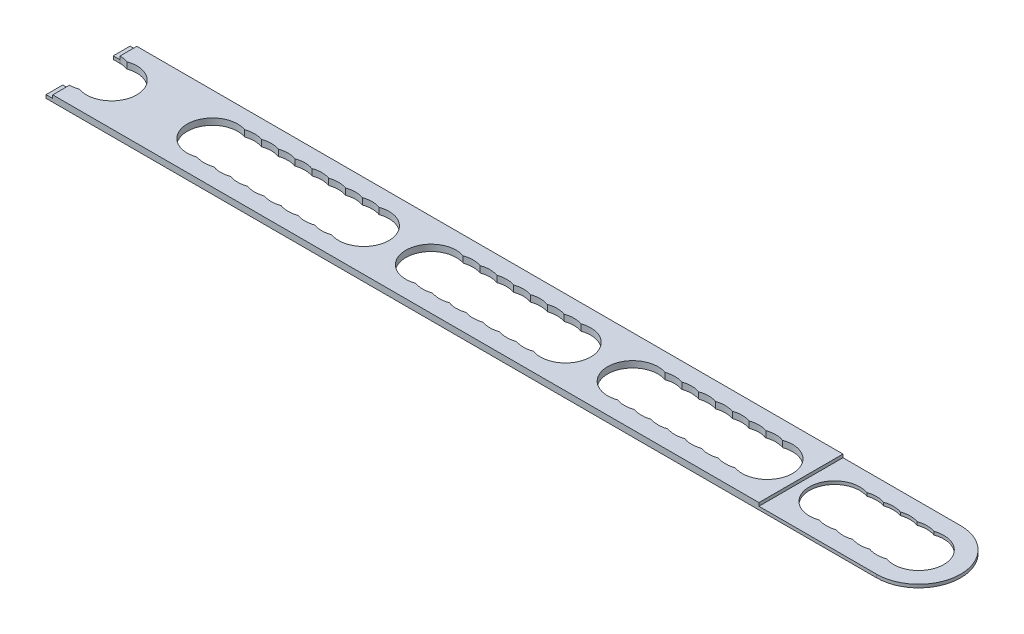
SolidWorks part; units mm, degrees
note: The reader was unsure of these and kept them because the rebuilt part matched: shared geometry of "Sketch1<3>".
ref_plane "Front Plane" through (0, 0, 0) normal (0, 0, 1) x (1, 0, 0)
ref_plane "Top Plane" through (0, 0, 0) normal (0, 1, 0) x (1, 0, 0)
ref_plane "Right Plane" through (0, 0, 0) normal (1, 0, 0) x (0, 0, -1)
sketch "Sketch1" plane through (0, 0, 0) normal (0, 1, 0) x (1, 0, 0)
  line L0 (-247.5, 0) -> (247.5, 0) construction
  line L1 (-247.5, -12.5) -> (247.5, -12.5)
  line L2 (-247.5, -12.5) -> (-247.5, 12.5)
  line L3 (-247.5, 12.5) -> (247.5, 12.5)
  line L4 (247.5, -12.5) -> (247.5, 12.5) construction
  line L5 (-247.5, -12.5) -> (247.5, 12.5) construction
  line L6 (-247.5, 12.5) -> (247.5, -12.5) construction
  line L7 (0, 12.5) -> (0, -12.5)
  line L8 (30, 12.5) -> (30, -12.5) construction
  line L9 (90, 12.5) -> (90, -12.5) construction
  line L10 (150, 12.5) -> (150, -12.5) construction
  line L11 (210, 12.5) -> (210, -12.5)
  arc A0 (-2.5, 7.0711) -> (2.5, 7.0711) centre (0, 0) cw
  arc A1 (2.5, 7.0711) -> (7.5, 7.0711) centre (5, 0) cw
  arc A2 (7.5, 7.0711) -> (12.5, 7.0711) centre (10, 0) cw
  arc A3 (12.5, 7.0711) -> (17.5, 7.0711) centre (15, 0) cw
  arc A4 (17.5, 7.0711) -> (22.5, 7.0711) centre (20, 0) cw
  arc A5 (22.5, 7.0711) -> (27.5, 7.0711) centre (25, 0) cw
  arc A6 (27.5, 7.0711) -> (32.5, 7.0711) centre (30, 0) cw
  arc A7 (32.5, 7.0711) -> (37.5, 7.0711) centre (35, 0) cw
  arc A8 (37.5, 7.0711) -> (42.5, 7.0711) centre (40, 0) cw
  arc A9 (42.5, 7.0711) -> (47.5, 7.0711) centre (45, 0) cw
  arc A10 (47.5, 7.0711) -> (52.5, 7.0711) centre (50, 0) cw
  arc A11 (52.5, 7.0711) -> (57.5, 7.0711) centre (55, 0) cw
  arc A12 (57.5, 7.0711) -> (62.5, 7.0711) centre (60, 0) cw
  arc A13 (62.5, 7.0711) -> (67.5, 7.0711) centre (65, 0) cw
  arc A14 (67.5, 7.0711) -> (72.5, 7.0711) centre (70, 0) cw
  arc A15 (72.5, 7.0711) -> (77.5, 7.0711) centre (75, 0) cw
  arc A16 (77.5, 7.0711) -> (82.5, 7.0711) centre (80, 0) cw
  arc A17 (82.5, 7.0711) -> (87.5, 7.0711) centre (85, 0) cw
  arc A18 (87.5, 7.0711) -> (92.5, 7.0711) centre (90, 0) cw
  arc A19 (92.5, 7.0711) -> (97.5, 7.0711) centre (95, 0) cw
  arc A20 (97.5, 7.0711) -> (102.5, 7.0711) centre (100, 0) cw
  arc A21 (102.5, 7.0711) -> (107.5, 7.0711) centre (105, 0) cw
  arc A22 (107.5, 7.0711) -> (112.5, 7.0711) centre (110, 0) cw
  arc A23 (112.5, 7.0711) -> (117.5, 7.0711) centre (115, 0) cw
  arc A24 (117.5, 7.0711) -> (122.5, 7.0711) centre (120, 0) cw
  arc A25 (122.5, 7.0711) -> (127.5, 7.0711) centre (125, 0) cw
  arc A26 (127.5, 7.0711) -> (132.5, 7.0711) centre (130, 0) cw
  arc A27 (132.5, 7.0711) -> (137.5, 7.0711) centre (135, 0) cw
  arc A28 (137.5, 7.0711) -> (142.5, 7.0711) centre (140, 0) cw
  arc A29 (142.5, 7.0711) -> (147.5, 7.0711) centre (145, 0) cw
  arc A30 (147.5, 7.0711) -> (152.5, 7.0711) centre (150, 0) cw
  arc A31 (152.5, 7.0711) -> (157.5, 7.0711) centre (155, 0) cw
  arc A32 (157.5, 7.0711) -> (162.5, 7.0711) centre (160, 0) cw
  arc A33 (162.5, 7.0711) -> (167.5, 7.0711) centre (165, 0) cw
  arc A34 (167.5, 7.0711) -> (172.5, 7.0711) centre (170, 0) cw
  arc A35 (172.5, 7.0711) -> (177.5, 7.0711) centre (175, 0) cw
  arc A36 (177.5, 7.0711) -> (182.5, 7.0711) centre (180, 0) cw
  arc A37 (182.5, 7.0711) -> (187.5, 7.0711) centre (185, 0) cw
  arc A38 (187.5, 7.0711) -> (192.5, 7.0711) centre (190, 0) cw
  arc A39 (192.5, 7.0711) -> (197.5, 7.0711) centre (195, 0) cw
  arc A40 (197.5, 7.0711) -> (202.5, 7.0711) centre (200, 0) cw
  arc A41 (202.5, 7.0711) -> (207.5, 7.0711) centre (205, 0) cw
  arc A42 (207.5, 7.0711) -> (212.5, 7.0711) centre (210, 0) cw
  arc A43 (212.5, 7.0711) -> (217.5, 7.0711) centre (215, 0) cw
  arc A44 (217.5, 7.0711) -> (222.5, 7.0711) centre (220, 0) cw
  arc A45 (222.5, 7.0711) -> (227.5, 7.0711) centre (225, 0) cw
  arc A46 (227.5, 7.0711) -> (232.5, 7.0711) centre (230, 0) cw
  arc A47 (232.5, 7.0711) -> (237.5, 7.0711) centre (235, 0) cw
  arc A48 (222.5, -7.0711) -> (227.5, -7.0711) centre (225, 0) ccw
  arc A49 (217.5, -7.0711) -> (222.5, -7.0711) centre (220, 0) ccw
  arc A50 (212.5, -7.0711) -> (217.5, -7.0711) centre (215, 0) ccw
  arc A51 (207.5, -7.0711) -> (212.5, -7.0711) centre (210, 0) ccw
  arc A52 (202.5, -7.0711) -> (207.5, -7.0711) centre (205, 0) ccw
  arc A53 (197.5, -7.0711) -> (202.5, -7.0711) centre (200, 0) ccw
  arc A54 (192.5, -7.0711) -> (197.5, -7.0711) centre (195, 0) ccw
  arc A55 (187.5, -7.0711) -> (192.5, -7.0711) centre (190, 0) ccw
  arc A56 (182.5, -7.0711) -> (187.5, -7.0711) centre (185, 0) ccw
  arc A57 (177.5, -7.0711) -> (182.5, -7.0711) centre (180, 0) ccw
  arc A58 (172.5, -7.0711) -> (177.5, -7.0711) centre (175, 0) ccw
  arc A59 (167.5, -7.0711) -> (172.5, -7.0711) centre (170, 0) ccw
  arc A60 (162.5, -7.0711) -> (167.5, -7.0711) centre (165, 0) ccw
  arc A61 (157.5, -7.0711) -> (162.5, -7.0711) centre (160, 0) ccw
  arc A62 (152.5, -7.0711) -> (157.5, -7.0711) centre (155, 0) ccw
  arc A63 (147.5, -7.0711) -> (152.5, -7.0711) centre (150, 0) ccw
  arc A64 (142.5, -7.0711) -> (147.5, -7.0711) centre (145, 0) ccw
  arc A65 (137.5, -7.0711) -> (142.5, -7.0711) centre (140, 0) ccw
  arc A66 (132.5, -7.0711) -> (137.5, -7.0711) centre (135, 0) ccw
  arc A67 (127.5, -7.0711) -> (132.5, -7.0711) centre (130, 0) ccw
  arc A68 (122.5, -7.0711) -> (127.5, -7.0711) centre (125, 0) ccw
  arc A69 (117.5, -7.0711) -> (122.5, -7.0711) centre (120, 0) ccw
  arc A70 (112.5, -7.0711) -> (117.5, -7.0711) centre (115, 0) ccw
  arc A71 (107.5, -7.0711) -> (112.5, -7.0711) centre (110, 0) ccw
  arc A72 (102.5, -7.0711) -> (107.5, -7.0711) centre (105, 0) ccw
  arc A73 (97.5, -7.0711) -> (102.5, -7.0711) centre (100, 0) ccw
  arc A74 (92.5, -7.0711) -> (97.5, -7.0711) centre (95, 0) ccw
  arc A75 (87.5, -7.0711) -> (92.5, -7.0711) centre (90, 0) ccw
  arc A76 (82.5, -7.0711) -> (87.5, -7.0711) centre (85, 0) ccw
  arc A77 (77.5, -7.0711) -> (82.5, -7.0711) centre (80, 0) ccw
  arc A78 (72.5, -7.0711) -> (77.5, -7.0711) centre (75, 0) ccw
  arc A79 (67.5, -7.0711) -> (72.5, -7.0711) centre (70, 0) ccw
  arc A80 (62.5, -7.0711) -> (67.5, -7.0711) centre (65, 0) ccw
  arc A81 (57.5, -7.0711) -> (62.5, -7.0711) centre (60, 0) ccw
  arc A82 (52.5, -7.0711) -> (57.5, -7.0711) centre (55, 0) ccw
  arc A83 (47.5, -7.0711) -> (52.5, -7.0711) centre (50, 0) ccw
  arc A84 (42.5, -7.0711) -> (47.5, -7.0711) centre (45, 0) ccw
  arc A85 (37.5, -7.0711) -> (42.5, -7.0711) centre (40, 0) ccw
  arc A86 (32.5, -7.0711) -> (37.5, -7.0711) centre (35, 0) ccw
  arc A87 (27.5, -7.0711) -> (32.5, -7.0711) centre (30, 0) ccw
  arc A88 (22.5, -7.0711) -> (27.5, -7.0711) centre (25, 0) ccw
  arc A89 (17.5, -7.0711) -> (22.5, -7.0711) centre (20, 0) ccw
  arc A90 (12.5, -7.0711) -> (17.5, -7.0711) centre (15, 0) ccw
  arc A91 (7.5, -7.0711) -> (12.5, -7.0711) centre (10, 0) ccw
  arc A92 (2.5, -7.0711) -> (7.5, -7.0711) centre (5, 0) ccw
  arc A93 (-2.5, -7.0711) -> (2.5, -7.0711) centre (0, 0) ccw
  arc A94 (237.5, 7.0711) -> (242.5, 7.0711) centre (240, 0) cw
  arc A96 (7.5, 7.0711) -> (7.5, -7.0711) centre (5, 0) cw
  arc A97 (32.5, 7.0711) -> (32.5, -7.0711) centre (35, 0) ccw
  arc A98 (82.5, 7.0711) -> (82.5, -7.0711) centre (80, 0) cw
  arc A99 (97.5, 7.0711) -> (97.5, -7.0711) centre (100, 0) ccw
  arc A100 (142.5, 7.0711) -> (142.5, -7.0711) centre (140, 0) cw
  arc A101 (157.5, 7.0711) -> (157.5, -7.0711) centre (160, 0) ccw
  arc A102 (242.5, 7.0711) -> (247.5, 7.0711) centre (245, 0) cw
  arc A103 (242.5, -7.0711) -> (247.5, -7.0711) centre (245, 0) ccw
  arc A104 (237.5, -7.0711) -> (242.5, -7.0711) centre (240, 0) ccw
  arc A105 (232.5, -7.0711) -> (237.5, -7.0711) centre (235, 0) ccw
  arc A106 (227.5, -7.0711) -> (232.5, -7.0711) centre (230, 0) ccw
  arc A107 (247.5, 7.0711) -> (247.5, -7.0711) centre (245, 0) cw
  arc A108 (245, 12.5) -> (245, -12.5) centre (245, 0) cw
  arc A109 (202.5, 7.0711) -> (202.4833, -7.077) centre (200, 0) cw
  arc A110 (217.5, 7.0711) -> (217.5, -7.0711) centre (220, 0) ccw
  point P0 (0, 0)
  dimension "D4" = 7.5
  dimension "D1" = 25
  dimension "D2" = 495
  dimension "D3" = 5
  dimension "D6" = 30
  dimension "D7" = 60
  dimension "D8" = 60
  dimension "D9" = 60
  dimension "D5" = 50
extrude "Boss-Extrude1" add sketch "Sketch1" along normal blind 1.9 contours A108 L3 L7 A0 A1 A2 A3 A4 A5 A6 A7 A8 A9 A10 A11 A12 A13 A14 A15 A16 A17 A18 A19 A20 A21 A22 A23 A24 A25 A26 A27 A28 A29 A30 A31 A32 A33 A34 A35 A36 A37 A38 A39 A40 A41 A42 A43 A44 A45 A46 A47 | A97 A6 A5 A4 A3 A2 A96 A91 A90 A89 A88 A87 | A99 A19 A18 A17 A98 A76 A75 A74 | A101 A31 A30 A29 A100 A64 A63 A62 | A110 A43 A42 A41 A109 A52 A51 A50 | A93 L7 L1 L11 A51 A52 A53 A54 A55 A56 A57 A58 A59 A60 A61 A62 A63 A64 A65 A66 A67 A68 A69 A70 A71 A72 A73 A74 A75 A76 A77 A78 A79 A80 A81 A82 A83 A84 A85 A86 A87 A88 A89 A90 A91 A92
extrude "Boss-Extrude3" add sketch "Sketch1<3>" along normal blind 0.95 contours A108 L3 L11 A42 A43 A44 A45 A46 A47 A94 A102 A107 A103 A104 A105 A106 A48 A49 A50 A51 L1 | A110 A43 A42 L11 A51 A50
sketch "Sketch1<3>" plane through (0, 0, 0) normal (0, 1, 0) x (1, 0, 0) same geometry as "Sketch1"
sketch "Sketch2" plane through (0, 0, 0) normal (0, 1, 0) x (1, 0, 0)
  line L1 (0, 12.5) -> (-2, 12.5)
  line L2 (0, 12.5) -> (0, 7.5)
  line L3 (0, 7.5) -> (-2, 7.5)
  line L4 (-2, 12.5) -> (-2, 7.5)
  line L5 (0, -12.5) -> (-2, -12.5)
  line L6 (0, -12.5) -> (0, -7.5)
  line L7 (0, -7.5) -> (-2, -7.5)
  line L8 (-2, -12.5) -> (-2, -7.5)
  dimension "D1" = 2
extrude "Boss-Extrude2" add sketch "Sketch2" along normal blind 0.95
equation "\"diameter_electrode_outer\"= 15mm"
equation "\"width_wing\"= 5mm"
equation "\"rad_curve\"= \"diameter_electrode_outer\" / 2"
equation "\"length_wing\"= 10mm"
equation "\"range_electrode_move_horizontal\"= ( \"length_wing\" / 2 ) * 66"
equation "\"length_slit_horizontal\"= \"diameter_electrode_outer\" + \"range_electrode_move_horizontal\""
equation "\"width_frame\"= \"diameter_electrode_outer\" + \"width_wing\" * 2"
equation "\"height_frame\"= 1.9mm"
equation "\"diameter_fluid_tank_outer\"= 60mm"
equation "\"width_frame_support\"= 10mm"
equation "\"range_electrode_move_vertical\"= ( \"length_wing\" / 2 ) * 75"
equation "\"length_slit_vertical\"= \"diameter_electrode_outer\" + \"range_electrode_move_vertical\""
equation "\"circumference_head\"= 600mm"
equation "\"range_electrode_move_front\"= \"circumference_head\" * 3.5 / 10"
equation "\"length_slit_front\"= \"range_electrode_move_front\" + \"diameter_electrode_outer\""
equation "\"width_connect\"= 2mm"
equation "\"height_connect\"= \"height_frame\" / 2"
equation "\"range_electrode_move_cir_back\"= \"circumference_head\" * 8 / 10"
equation "\"length_slit_back\"= \"range_electrode_move_cir_back\" + \"diameter_electrode_outer\""
equation "\"D1@Sketch1\"=\"diameter_electrode_outer\"+\"width_wing\"*2"
equation "\"D2@Sketch1\"=\"length_slit_back\""
equation "\"D3@Sketch1\"=\"length_wing\"/2"
equation "\"D4@Sketch1\"=\"rad_curve\""
equation "\"D6@Sketch1\"=\"circumference_head\"/20"
equation "\"D7@Sketch1\"=\"circumference_head\"/10"
equation "\"D8@Sketch1\"=\"circumference_head\"/10"
equation "\"D9@Sketch1\"=\"circumference_head\"/10"
equation "\"D1@Boss-Extrude1\"=\"height_frame\""
equation "\"D1@Sketch2\"=\"width_connect\""
equation "\"D1@Boss-Extrude2\"=\"height_connect\""
equation "\"D1@Boss-Extrude3\"=\"height_frame\"/2"
